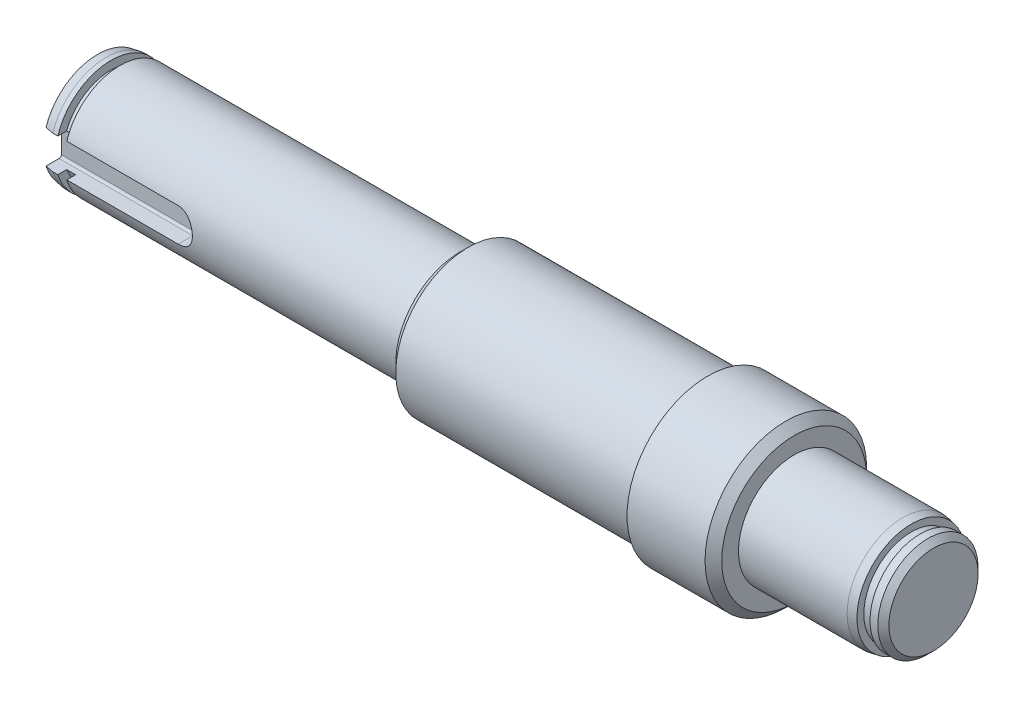
SolidWorks part; units mm, degrees
material "Простая углеродистая сталь"
ref_plane "Спереди" through (0, 0, 0) normal (0, 0, 1) x (1, 0, 0)
ref_plane "Сверху" through (0, 0, 0) normal (0, 1, 0) x (1, 0, 0)
ref_plane "Справа" through (0, 0, 0) normal (1, 0, 0) x (0, 0, -1)
sketch "Эскиз1" plane through (0, 0, 0) normal (0, 0, 1) x (1, 0, 0)
  line L0 (0, 0) -> (0, 13)
  line L1 (0, 13) -> (30, 13)
  line L2 (30, 13) -> (30, 10)
  line L3 (30, 10) -> (51, 10)
  line L4 (51, 10) -> (51, 9)
  line L5 (51, 9) -> (55, 9)
  line L6 (0, 0) -> (55, 0)
  line L7 (55, 9) -> (55, 0)
  dimension "D1" = 30
  dimension "D2" = 21
  dimension "D3" = 4
  dimension "D4" = 13
  dimension "D5" = 10
  dimension "D6" = 9
revolve "Повернуть1" add sketch "Эскиз1" angle 360 about L6
mirror "Зеркальное отражение1" about plane through (0, 0, 0) normal (1, 0, 0) of bodies 103
chamfer "Фаска1" distance 1.5 angle 10 1 edges at (51, 0, 10) first distance on face at (30, 0, 10)
chamfer "Фаска2" distance 1 angle 45 1 edges at (55, 0, 9)
sketch "Эскиз2" plane through (0, 0, 0) normal (0, 1, 0) x (1, 0, 0)
  line L1 (51, 8.5) -> (52.6, 8.5)
  line L2 (51, 8.5) -> (51, 10.9087)
  line L3 (51, 10.9087) -> (52.6, 10.9087)
  line L4 (52.6, 8.5) -> (52.6, 10.9087)
  line L5 (0, 0) -> (55, 0) construction
  line L6 (55, -8) -> (55, 8) construction
  line L8 (51, -9) -> (51, 9) construction
  dimension "D1" = 8.5
  dimension "D2" = 1.6
revolve "Вырез-Повернуть1" cut sketch "Эскиз2" angle 360 about L5
mirror "Зеркальное отражение2" about plane through (0, 0, 0) normal (1, 0, 0) of "Вырез-Повернуть1"
ref_axis "Ось1" through (48.5549, 0, 0) along (-1, 0, 0)
sketch "Эскиз6" plane through (-52.6, 0, 0) normal (1, 0, 0) x (0, 0, -1)
  circle A1 centre (0, 0) radius 10
  dimension "D1" = 20
extrude "Бобышка-Вытянуть2" add sketch "Эскиз6" against normal blind 42.4 and the other way up to surface
chamfer "Фаска5" distance 1.5 angle 10 1 edges at (-95, 0, -10) first distance on face at (-30, 0, 10)
ref_plane "Плоскость1" through (-20, 0, 0) normal (1, 0, 0) x (0, 0, -1)
mirror "Зеркальное отражение5" about plane through (-20, 0, 0) normal (1, 0, 0) of "Вырез-Повернуть1"
ref_plane "Плоскость2" through (0, 0, 10) normal (0, 0, 1) x (1, 0, 0)
sketch "Эскиз8" plane through (0, 0, 10) normal (0, 0, 1) x (1, 0, 0)
  line L0 (-119, 0) -> (-71, 0) construction
  line L1 (-95, 9.7355) -> (-95, -9.7355) construction
  line L2 (-119, 3) -> (-71, 3)
  line L3 (-119, -3) -> (-71, -3)
  arc A0 (-119, 3) -> (-119, -3) centre (-119, 0) ccw
  arc A1 (-71, -3) -> (-71, 3) centre (-71, 0) ccw
  point P5 (-95, 0)
  dimension "D1" = 6
  dimension "D2" = 24
extrude "Вырез-Вытянуть2" cut sketch "Эскиз8" against normal blind 3.5
chamfer "Фаска6" distance 1.5 angle 45 1 edges at (-30, 0, 13)
sketch "Эскиз9" plane through (30, 0, 0) normal (1, 0, 0) x (0, 0, -1)
  circle A0 centre (0, 0) radius 13 construction
  circle A1 centre (0, 0) radius 13
  circle A2 centre (0, 0) radius 14.5
  dimension "D1" = 1.5
extrude "Бобышка-Вытянуть3" add sketch "Эскиз9" against normal blind 15.5
chamfer "Фаска7" distance 1.5 angle 45 1 edges at (30, 0, -14.5)
fillet "Скругление1" radius 0.4 3 edges at (-83, 3, 6.5) (-68, 0, 6.5) (-83, -3, 6.5)
